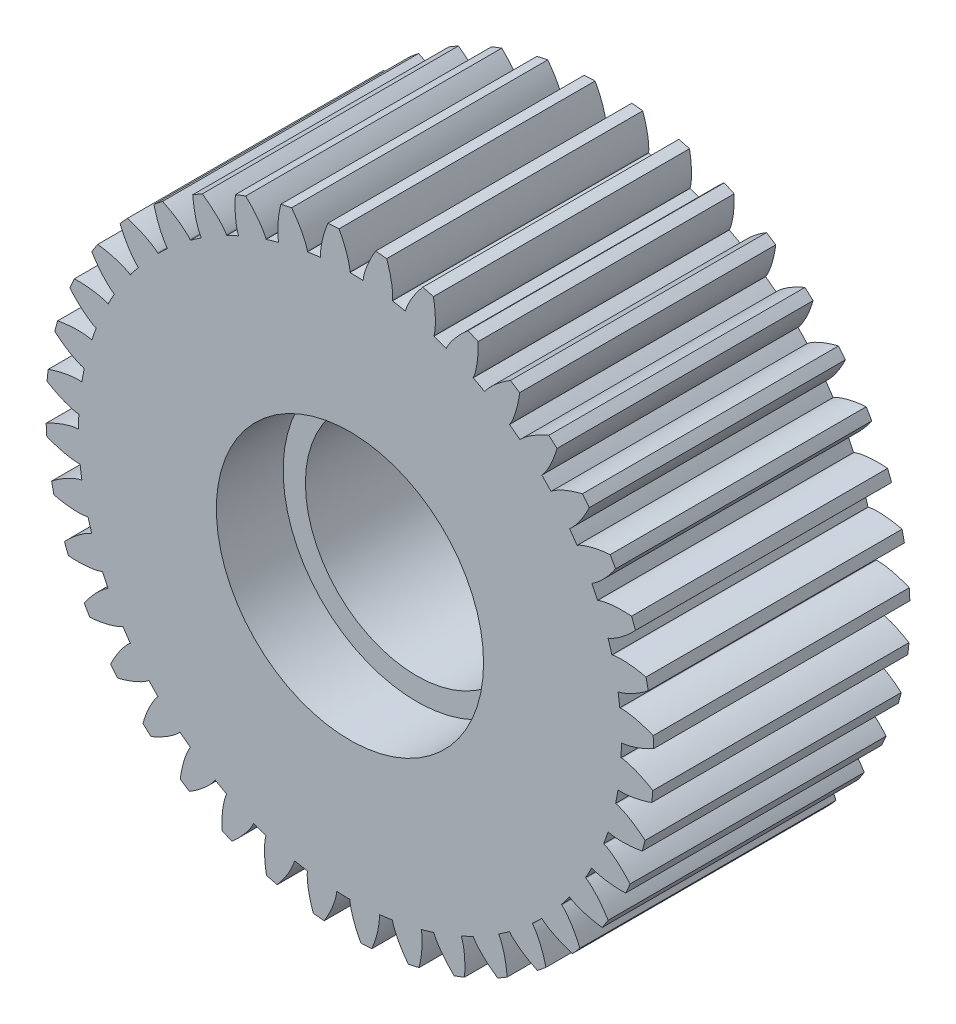
SolidWorks part; units mm, degrees
ref_plane "Front Plane" through (0, 0, 0) normal (0, 0, 1) x (1, 0, 0)
ref_plane "Top Plane" through (0, 0, 0) normal (0, 1, 0) x (1, 0, 0)
ref_plane "Right Plane" through (0, 0, 0) normal (1, 0, 0) x (0, 0, -1)
sketch "Sketch1" plane through (0, 0, 0) normal (0, 0, 1) x (1, 0, 0)
  circle A0 centre (0, 0) radius 13.65
  dimension "D1" = 27.3
extrude "Boss-Extrude1" add sketch "Sketch1" along normal mid plane 11.5
sketch "Sketch2" plane through (0, 0, 0) normal (0, 0, 1) x (1, 0, 0)
  line L0 (0, 0) -> (12.216, 0) construction
  line L1 (0, 0) -> (12.9961, -0.3167) construction
  line L2 (0, 0) -> (12.2015, -0.5951) construction
  line L3 (12.216, 0) -> (12.1875, 0)
  line L4 (12.2015, -0.5951) -> (12.173, -0.5937)
  circle A0 centre (0, 0) radius 13 construction
  circle A1 centre (0, 0) radius 12.216 construction
  circle A2 centre (0, 0) radius 12.1875
  circle A3 centre (0, 0) radius 13.65 construction
  circle A4 centre (0, 0) radius 13.65
  spline S0 degree 4 poles (12.216, 0) (12.2202, 0.0001) (12.2319, 0.0004) (12.254, 0.0018) (12.2901, 0.0052) (12.3359, 0.0109) (12.395, 0.0202) (12.4644, 0.0333) (12.5405, 0.0501) (12.6228, 0.0708) (12.7047, 0.0938) (12.786, 0.1188) (12.8667, 0.1455) (12.9639, 0.1801) (13.08, 0.2247) (13.2146, 0.2811) (13.366, 0.3503) (13.5189, 0.4264) (13.6681, 0.5057) (13.8173, 0.591) (13.9606, 0.6771) (14.1076, 0.7717) (14.2425, 0.8617) (14.3915, 0.9681) (14.5112, 1.0557) (14.6668, 1.1772) (14.758, 1.2507) (14.8638, 1.3388) (14.9104, 1.3789) (14.9391, 1.4036) knots 0 0 0 0 0 0.005377 0.015084 0.028532 0.04661 0.064855 0.092111 0.119476 0.146842 0.174209 0.201575 0.228941 0.256307 0.307035 0.361767 0.4165 0.471232 0.525964 0.580697 0.635429 0.690161 0.744894 0.799626 0.854358 0.909091 0.954545 1 1 1 1 1 construction
  spline S1 degree 4 poles (12.216, 0) (12.2202, 0.0001) (12.2319, 0.0004) (12.254, 0.0018) (12.2901, 0.0052) (12.3359, 0.0109) (12.395, 0.0202) (12.4644, 0.0333) (12.5405, 0.0501) (12.6228, 0.0708) (12.7047, 0.0938) (12.786, 0.1188) (12.8667, 0.1455) (12.9639, 0.1801) (13.08, 0.2247) (13.2146, 0.2811) (13.366, 0.3503) (13.5189, 0.4264) (13.6681, 0.5057) (13.8173, 0.591) (13.9606, 0.6771) (14.1076, 0.7717) (14.2425, 0.8617) (14.3915, 0.9681) (14.5112, 1.0557) (14.6331, 1.1508) (14.6921, 1.1978) (14.7221, 1.2221) knots 0 0 0 0 0 0.005377 0.015084 0.028532 0.04661 0.064855 0.092111 0.119476 0.146842 0.174209 0.201575 0.228941 0.256307 0.307035 0.361767 0.4165 0.471232 0.525964 0.580697 0.635429 0.690161 0.744894 0.799626 0.854358 0.909091 0.909091 0.909091 0.909091 0.909091
  spline S2 degree 4 poles (12.2015, -0.5951) (12.2057, -0.5953) (12.2173, -0.5963) (12.2394, -0.5987) (12.2752, -0.6038) (12.3207, -0.6118) (12.3793, -0.6239) (12.448, -0.6404) (12.5231, -0.6609) (12.6044, -0.6856) (12.685, -0.7126) (12.765, -0.7415) (12.8443, -0.7721) (12.9398, -0.8114) (13.0535, -0.8616) (13.1852, -0.9245) (13.3331, -1.001) (13.4821, -1.0844) (13.6273, -1.1709) (13.7721, -1.2633) (13.911, -1.3563) (14.0533, -1.458) (14.1836, -1.5544) (14.3273, -1.668) (14.4426, -1.7613) (14.592, -1.8902) (14.6795, -1.9681) (14.781, -2.0612) (14.8255, -2.1036) (14.853, -2.1297) knots 0 0 0 0 0 0.005377 0.015084 0.028532 0.04661 0.064855 0.092111 0.119476 0.146842 0.174209 0.201575 0.228941 0.256307 0.307035 0.361767 0.4165 0.471232 0.525964 0.580697 0.635429 0.690161 0.744894 0.799626 0.854358 0.909091 0.954545 1 1 1 1 1 construction
  spline S3 degree 4 poles (12.2015, -0.5951) (12.2057, -0.5953) (12.2173, -0.5963) (12.2394, -0.5987) (12.2752, -0.6038) (12.3207, -0.6118) (12.3793, -0.6239) (12.448, -0.6404) (12.5231, -0.6609) (12.6044, -0.6856) (12.685, -0.7126) (12.765, -0.7415) (12.8443, -0.7721) (12.9398, -0.8114) (13.0535, -0.8616) (13.1852, -0.9245) (13.3331, -1.001) (13.4821, -1.0844) (13.6273, -1.1709) (13.7721, -1.2633) (13.911, -1.3563) (14.0533, -1.458) (14.1836, -1.5544) (14.3273, -1.668) (14.4426, -1.7613) (14.5596, -1.8623) (14.6163, -1.9121) (14.6451, -1.9378) knots 0 0 0 0 0 0.005377 0.015084 0.028532 0.04661 0.064855 0.092111 0.119476 0.146842 0.174209 0.201575 0.228941 0.256307 0.307035 0.361767 0.4165 0.471232 0.525964 0.580697 0.635429 0.690161 0.744894 0.799626 0.854358 0.909091 0.909091 0.909091 0.909091 0.909091
  dimension "D1" = 26
  dimension "D2" = 24.432
  dimension "D3" = 24.375
  dimension "D4" = 1.396
  dimension "D5" = 1.396
extrude "Cut-Extrude1" cut sketch "Sketch2" against normal through all both and the other way through all contours A2 S3 A4 S1 region at (13.0417, -0.3178, 0)
pattern_circular "CirPattern2" count 40 over 360 about axis through (0, 0, 5.75) along (0, 0, -1) of "Cut-Extrude1"
sketch "Sketch3" plane through (0, 0, 5.75) normal (0, 0, 1) x (1, 0, 0)
  circle A0 centre (0, 0) radius 6
  dimension "D1" = 12
extrude "Cut-Extrude2" cut sketch "Sketch3" against normal blind 3
sketch "Sketch4" plane through (0, 0, 2.75) normal (0, 0, 1) x (1, 0, 0)
  circle A0 centre (0, 0) radius 5
  dimension "D1" = 10
extrude "Cut-Extrude3" cut sketch "Sketch4" against normal through all
mirror "Mirror1" about plane through (0, 0, 0) normal (0, 0, 1) of "Cut-Extrude2"
equation "\"Np\"= 40"
equation "\"module\"= 0.65"
equation "\"pressure angle\"= 20deg"
equation "\"h_a\"= 1 * \"module\"'addendum"
equation "\"h_b\"= 1.25 * \"module\"'dedendum"
equation "\"clr_tip_root\"= \"h_f\" - \"h_a\"'clearance of gear tooth tip and root"
equation "\"dp_p\"= \"module\" * \"Np\"'PCD"
equation "\"db_p\"= \"dp_p\" * cos ( \"pressure angle\" )'base CD"
equation "\"D1@Sketch1\"= \"dp_p\" + 2*\"h_a\" "
equation "\"fw_p\"= \"fw_r\""
equation "\"D1@Boss-Extrude1\"=\"fw_p\""
equation "\"D1@Sketch2\"=\"dp_p\""
equation "\"D2@Sketch2\"= \"db_p\""
equation "\"D3@Sketch2\"=\"dp_p\"- 2*\"h_b\""
equation "\"alpha_p\"= sqr ( \"dp_p\" ^ 2 - \"db_p\" ^ 2 ) / \"db_p\" * 180 / pi - \"pressure angle\""
equation "\"D4@Sketch2\"= 360 / ( 4 * \"Np\" ) - \"alpha_p\""
equation "\"beta_p\"= ( 360 / ( 4 * \"Np\" ) - \"alpha_p\" ) * 2"
equation "\"D5@Sketch2\"= 360 / ( 4 * \"Np\" ) - \"alpha_p\""
equation "\"D1@CirPattern2\"=\"Np\""
equation "\"Nr\"= \"Ns\" + 2 * \"Np\"'num teeth"
equation "\"pressure_angle\"= 20deg"
equation "\"h_f\"= 1.25 * \"module\"'dedendum"
equation "\"dp_r\"= \"module\" * \"Nr\"'PCD"
equation "\"db_r\"= \"dp_r\" * cos ( \"pressure_angle\" )'base CD"
equation "\"fw_r\"= 11.5mm'face width"
equation "\"alpha_r\"= sqr ( \"dp_r\" ^ 2 - \"db_r\" ^ 2 ) / \"db_r\" * 180 / pi - \"pressure_angle\""
equation "\"beta_r\"= ( 360 / ( 4 * \"Nr\" ) + \"alpha_r\" ) * 2"
equation "\"bearing_ID\"= \"module\" * ( \"Ns\" + \"Np\" ) + 10"
equation "\"bearing_OD\"= 1.18 * \"bearing_ID\" + 8.57"
equation "\"bearing_height\"= 0.09 * \"bearing_ID\" + 4.62"
equation "\"clearance_planet\"=1.5"
equation "\"case_dist\"= \"sec_carrier_thickness\" + \"clearance_planet\" + \"sun_coupler_hub_thickness\" - \"case_mounting_surface_height\""
equation "\"Motor_case_OD_max\"= \"case_mounting_PCD\" + \"case_mounting_hole_allen_socket_dia\" + \"clearance_case_mount_holes_shell_thickness\" * 2"
equation "\"case_mounting_PCD\"= \"motor_case_OD_base\" + \"case_mounting_hole_shift\" * 2"
equation "\"bearing mount thickness\"= \"output_mounting_hole_dia\" * 2"
equation "\"case_mounting_hole_dia\"=3"
equation "\"output_mounting_PCD\"= \"bearing_OD\" + \"bearing mount thickness\""
equation "\"output_mounting_hole_dia\"= 4"
equation "\"clearance_case_mount_holes_shell_thickness\"= 1"
equation "\"motor_case_OD_base\"= \"motor_OD\" + \"clearance_motor_and_case\" * 2 + \"Motor_case_thickness\" * 2"
equation "\"sec_carrier_thickness\"= 5"
equation "\"sun_coupler_hub_thickness\"= 4"
equation "\"clearance_sun_coupler_sec_carrier\"= 1.5"
equation "\"clearance_motor_and_case\"= 2.2"
equation "\"motor_OD\"= 72"
equation "\"Motor_case_thickness\"= 2"
equation "\"Motor_case_ID\"= \"motor_OD\" + \"clearance_motor_and_case\" * 2"
equation "\"case_mounting_hole_shift\"= \"case_mounting_hole_dia\" / 2 - 0.5"
equation "\"output_mounting_nut_wrench_size\"= 7"
equation "\"output_mounting_nut_thickness\"= 3.2"
equation "\"case_mounting_hole_allen_socket_dia\"= 5.5"
equation "\"output_mounting_nut_depth\"= 3"
equation "\"case_mounting_bolt_depth\"= 4.5"
equation "\"Ns\"= 20"
equation "\"ring_radial_thickness\"= 5"
equation "\"ring_OD\"= \"Nr\" * \"module\" + \"ring_radial_thickness\" * 2"
equation "\"ring_to_chamfer_clearance\"= 2"
equation "\"Motor_case_OD_base_to_chamfer\"=5"
equation "\"pattern_offset_from_motor_case_OD_base\"= 3"
equation "\"pattern_bulge_dia\"= 3"
equation "\"pattern_num_bulge\"= 18"
equation "\"pattern_depth\"= 2"
equation "\"motor_height\"= 27"
equation "\"case_mounting_wrench_size\"= 5.5"
equation "\"case_mounting_nut_clearance\"= 2"
equation "\"base_plate_thickness\"= 4"
equation "\"case_mounting_nut_thickness\"= 2.4"
equation "\"case_mounting_surface_height\"= 4"
equation "\"motor_mount_hole_PCD\"= 32"
equation "\"motor_mount_hole_dia\"= 4"
equation "\"motor_mount_hole_num\"= 4"
equation "\"central_hole_offset_from_motor_mount_PCD\"= 5"
equation "\"wire_slot_dist_from_center\"= 30"
equation "\"wire_slot_length\"= 10"
equation "\"wire_slot_radius\"= 4"
equation "\"driver_upper_holes_dist_from_center\"= 23"
equation "\"driver_lower_holes_dist_from_center\"= 15"
equation "\"driver_side_holes_dist_from_center\"= 20"
equation "\"driver_mount_holes_dia\"= 2.5"
equation "\"driver_mount_inserts_OD\"= 3.5"
equation "\"driver_mount_thickness\"= 1.5"
equation "\"driver_mount_height\"= 4"
equation "\"air_flow_hole_offset\"= 3"
equation "\"num_planet\"= 3"
equation "\"planet_pin_bolt_dia\"= 5"
equation "\"planet_pin_socket_head_dia\"= 8.5"
equation "\"carrier_PCD\"= ( \"Np\" + \"Ns\" ) * \"module\""
equation "\"planet_shaft_dia\"= 8"
equation "\"planet_shaft_step_offset\"= 1"
equation "\"carrier_trapezoidal_support_sun_offset\"= 5"
equation "\"carrier_trapezoidal_support_hole_PCD_offset_bearing_ID\"= 4"
equation "\"carrier_trapezoidal_support_hole_dia\"= 3"
equation "\"carrier_trapezoidal_support_hole_socket_head_dia\"= 5.5"
equation "\"carrier_bearing_step_width\"= 1.5"
equation "\"standard_clearance_1_5mm\"=1.5"
equation "\"standard_fillet_1_5mm\"= 1.5"
equation "\"sun_shaft_bearing_OD\"= 16"
equation "\"sun_shaft_bearing_width\"= 4"
equation "\"standard_bearing_insertion_chamfer\"= 0.5"
equation "\"carrier_trapezoidal_support_hole_wrench_size\"= 5.5"
equation "\"planet_pin_bolt_wrench_size\"= 8"
equation "\"planet_bearing_OD\"= 12"
equation "\"planet_bearing_width\"= 3"
equation "\"planet_bore\"= 10"
equation "\"D1@Cut-Extrude2\"=\"planet_bearing_width\""
equation "\"D1@Sketch3\"=\"planet_bearing_OD\""
equation "\"D1@Sketch4\"=\"planet_bore\""
